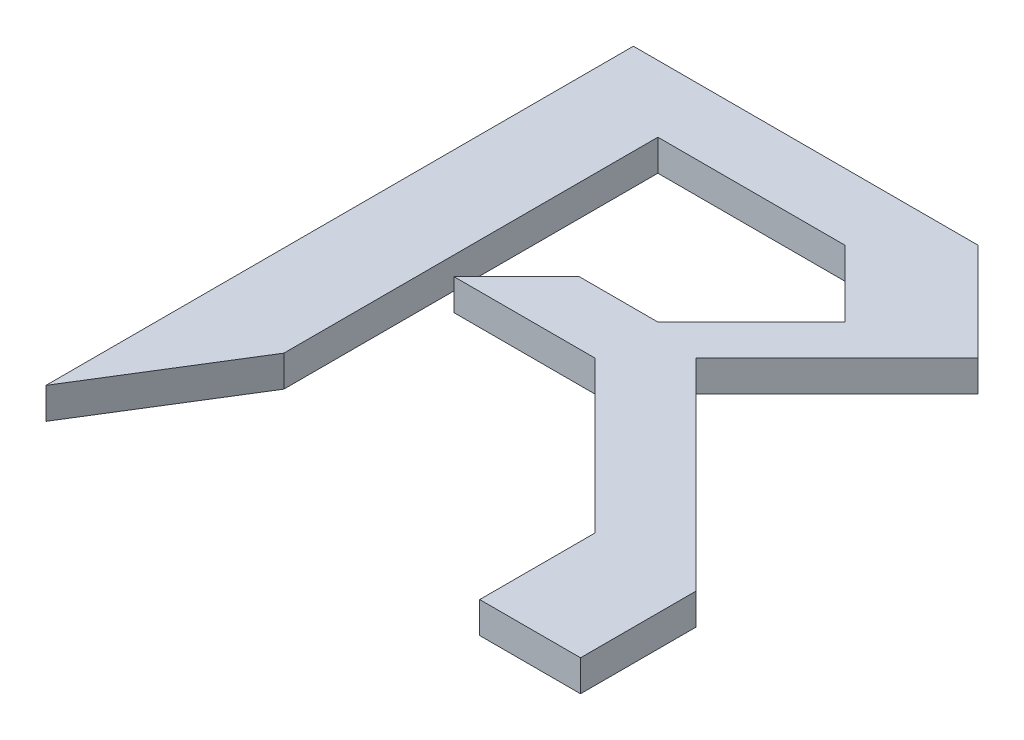
SolidWorks part; units mm, degrees
ref_plane "Front Plane" through (0, 0, 0) normal (0, 0, 1) x (1, 0, 0)
ref_plane "Top Plane" through (0, 0, 0) normal (0, 1, 0) x (1, 0, 0)
ref_plane "Right Plane" through (0, 0, 0) normal (1, 0, 0) x (0, 0, -1)
sketch "Sketch1" plane through (0, 0, 0) normal (0, 1, 0) x (1, 0, 0)
  line L0 (-339.9155, 126.1175) -> (-339.9155, 314.333)
  line L1 (-339.9155, 314.333) -> (-229.4957, 314.333)
  line L2 (-229.4957, 314.333) -> (-198.1265, 282.9637)
  line L3 (-198.1265, 282.9637) -> (-243.2982, 237.792)
  line L4 (-243.2982, 237.792) -> (-178.6775, 173.1713)
  line L5 (-178.6775, 173.1713) -> (-178.6775, 136.1556)
  line L6 (-178.6775, 136.1556) -> (-210.9879, 136.1556)
  line L7 (-210.9879, 136.1556) -> (-210.9879, 173.1713)
  line L8 (-210.9879, 173.1713) -> (-259.4534, 221.6368)
  line L9 (-259.4534, 221.6368) -> (-304.7819, 221.6368)
  line L10 (-304.7819, 221.6368) -> (-284.7056, 241.7132)
  line L11 (-284.7056, 241.7132) -> (-259.4534, 241.7132)
  line L12 (-259.4534, 241.7132) -> (-229.4957, 271.6708)
  line L13 (-229.4957, 271.6708) -> (-250.8268, 293.0019)
  line L14 (-250.8268, 293.0019) -> (-310.7421, 293.0019)
  line L15 (-310.7421, 293.0019) -> (-310.7421, 173.1713)
  line L16 (-310.7421, 173.1713) -> (-339.9155, 126.1175)
  point P2 (0, 0)
  point P18 (0, 0)
extrude "Boss-Extrude1" add sketch "Sketch1" along normal blind 10 contours L0 L1 L2 L3 L4 L5 L6 L7 L8 L9 L10 L11 L12 L13 L14 L15 L16
